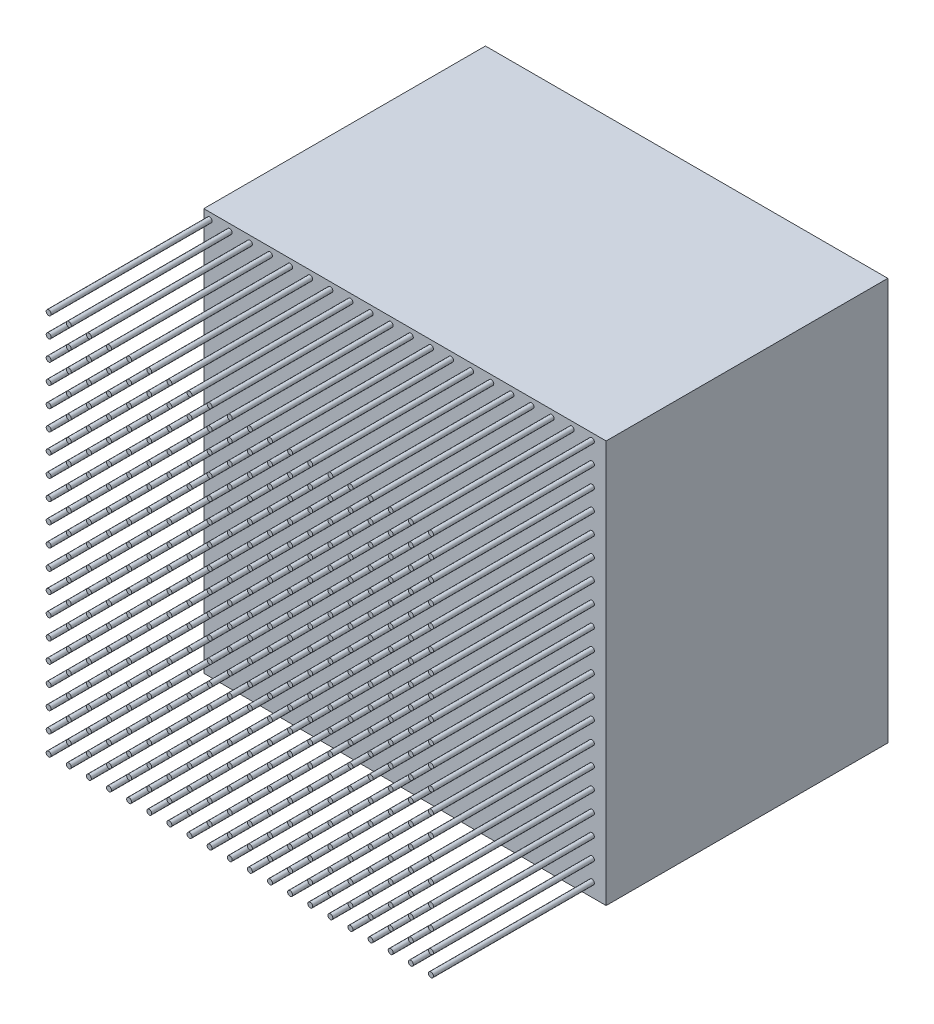
SolidWorks part; units mm, degrees
ref_plane "Front Plane" through (0, 0, 0) normal (0, 0, 1) x (1, 0, 0)
ref_plane "Top Plane" through (0, 0, 0) normal (0, 1, 0) x (1, 0, 0)
ref_plane "Right Plane" through (0, 0, 0) normal (1, 0, 0) x (0, 0, -1)
sketch "Sketch1" plane through (0, 0, 0) normal (0, 0, 1) x (1, 0, 0)
  line L1 (-50, -50) -> (50, -50)
  line L2 (-50, -50) -> (-50, 50)
  line L3 (-50, 50) -> (50, 50)
  line L4 (50, -50) -> (50, 50)
  line L5 (-50, -50) -> (50, 50) construction
  line L6 (-50, 50) -> (50, -50) construction
  point P0 (0, 0)
  dimension "D1" = 100
  dimension "D2" = 100
extrude "Boss-Extrude1" add sketch "Sketch1" along normal blind 70
sketch "Sketch2" plane through (0, 0, 70) normal (0, 0, 1) x (1, 0, 0)
  circle A0 centre (-48.544, 48.3318) radius 0.6164
  circle A1 centre (-43.544, 48.3318) radius 0.6164
  circle A2 centre (-38.544, 48.3318) radius 0.6164
  circle A3 centre (-33.544, 48.3318) radius 0.6164
  circle A4 centre (-28.544, 48.3318) radius 0.6164
  circle A5 centre (-23.544, 48.3318) radius 0.6164
  circle A6 centre (-18.544, 48.3318) radius 0.6164
  circle A7 centre (-13.544, 48.3318) radius 0.6164
  circle A8 centre (-8.544, 48.3318) radius 0.6164
  circle A9 centre (-3.544, 48.3318) radius 0.6164
  circle A10 centre (1.456, 48.3318) radius 0.6164
  circle A11 centre (6.456, 48.3318) radius 0.6164
  circle A12 centre (11.456, 48.3318) radius 0.6164
  circle A13 centre (16.456, 48.3318) radius 0.6164
  circle A14 centre (21.456, 48.3318) radius 0.6164
  circle A15 centre (26.456, 48.3318) radius 0.6164
  circle A16 centre (31.456, 48.3318) radius 0.6164
  circle A17 centre (36.456, 48.3318) radius 0.6164
  circle A18 centre (41.456, 48.3318) radius 0.6164
  circle A19 centre (46.456, 48.3318) radius 0.6164
  circle A20 centre (-43.544, 43.3318) radius 0.6164
  circle A21 centre (-38.544, 43.3318) radius 0.6164
  circle A22 centre (-33.544, 43.3318) radius 0.6164
  circle A23 centre (-28.544, 43.3318) radius 0.6164
  circle A24 centre (-23.544, 43.3318) radius 0.6164
  circle A25 centre (-18.544, 43.3318) radius 0.6164
  circle A26 centre (-13.544, 43.3318) radius 0.6164
  circle A27 centre (-8.544, 43.3318) radius 0.6164
  circle A28 centre (-3.544, 43.3318) radius 0.6164
  circle A29 centre (1.456, 43.3318) radius 0.6164
  circle A30 centre (6.456, 43.3318) radius 0.6164
  circle A31 centre (11.456, 43.3318) radius 0.6164
  circle A32 centre (16.456, 43.3318) radius 0.6164
  circle A33 centre (21.456, 43.3318) radius 0.6164
  circle A34 centre (26.456, 43.3318) radius 0.6164
  circle A35 centre (31.456, 43.3318) radius 0.6164
  circle A36 centre (36.456, 43.3318) radius 0.6164
  circle A37 centre (41.456, 43.3318) radius 0.6164
  circle A38 centre (46.456, 43.3318) radius 0.6164
  circle A39 centre (-43.544, 38.3318) radius 0.6164
  circle A40 centre (-38.544, 38.3318) radius 0.6164
  circle A41 centre (-33.544, 38.3318) radius 0.6164
  circle A42 centre (-28.544, 38.3318) radius 0.6164
  circle A43 centre (-23.544, 38.3318) radius 0.6164
  circle A44 centre (-18.544, 38.3318) radius 0.6164
  circle A45 centre (-13.544, 38.3318) radius 0.6164
  circle A46 centre (-8.544, 38.3318) radius 0.6164
  circle A47 centre (-3.544, 38.3318) radius 0.6164
  circle A48 centre (1.456, 38.3318) radius 0.6164
  circle A49 centre (6.456, 38.3318) radius 0.6164
  circle A50 centre (11.456, 38.3318) radius 0.6164
  circle A51 centre (16.456, 38.3318) radius 0.6164
  circle A52 centre (21.456, 38.3318) radius 0.6164
  circle A53 centre (26.456, 38.3318) radius 0.6164
  circle A54 centre (31.456, 38.3318) radius 0.6164
  circle A55 centre (36.456, 38.3318) radius 0.6164
  circle A56 centre (41.456, 38.3318) radius 0.6164
  circle A57 centre (46.456, 38.3318) radius 0.6164
  circle A58 centre (-43.544, 33.3318) radius 0.6164
  circle A59 centre (-38.544, 33.3318) radius 0.6164
  circle A60 centre (-33.544, 33.3318) radius 0.6164
  circle A61 centre (-28.544, 33.3318) radius 0.6164
  circle A62 centre (-23.544, 33.3318) radius 0.6164
  circle A63 centre (-18.544, 33.3318) radius 0.6164
  circle A64 centre (-13.544, 33.3318) radius 0.6164
  circle A65 centre (-8.544, 33.3318) radius 0.6164
  circle A66 centre (-3.544, 33.3318) radius 0.6164
  circle A67 centre (1.456, 33.3318) radius 0.6164
  circle A68 centre (6.456, 33.3318) radius 0.6164
  circle A69 centre (11.456, 33.3318) radius 0.6164
  circle A70 centre (16.456, 33.3318) radius 0.6164
  circle A71 centre (21.456, 33.3318) radius 0.6164
  circle A72 centre (26.456, 33.3318) radius 0.6164
  circle A73 centre (31.456, 33.3318) radius 0.6164
  circle A74 centre (36.456, 33.3318) radius 0.6164
  circle A75 centre (41.456, 33.3318) radius 0.6164
  circle A76 centre (46.456, 33.3318) radius 0.6164
  circle A77 centre (-43.544, 28.3318) radius 0.6164
  circle A78 centre (-38.544, 28.3318) radius 0.6164
  circle A79 centre (-33.544, 28.3318) radius 0.6164
  circle A80 centre (-28.544, 28.3318) radius 0.6164
  circle A81 centre (-23.544, 28.3318) radius 0.6164
  circle A82 centre (-18.544, 28.3318) radius 0.6164
  circle A83 centre (-13.544, 28.3318) radius 0.6164
  circle A84 centre (-8.544, 28.3318) radius 0.6164
  circle A85 centre (-3.544, 28.3318) radius 0.6164
  circle A86 centre (1.456, 28.3318) radius 0.6164
  circle A87 centre (6.456, 28.3318) radius 0.6164
  circle A88 centre (11.456, 28.3318) radius 0.6164
  circle A89 centre (16.456, 28.3318) radius 0.6164
  circle A90 centre (21.456, 28.3318) radius 0.6164
  circle A91 centre (26.456, 28.3318) radius 0.6164
  circle A92 centre (31.456, 28.3318) radius 0.6164
  circle A93 centre (36.456, 28.3318) radius 0.6164
  circle A94 centre (41.456, 28.3318) radius 0.6164
  circle A95 centre (46.456, 28.3318) radius 0.6164
  circle A96 centre (-43.544, 23.3318) radius 0.6164
  circle A97 centre (-38.544, 23.3318) radius 0.6164
  circle A98 centre (-33.544, 23.3318) radius 0.6164
  circle A99 centre (-28.544, 23.3318) radius 0.6164
  circle A100 centre (-23.544, 23.3318) radius 0.6164
  circle A101 centre (-18.544, 23.3318) radius 0.6164
  circle A102 centre (-13.544, 23.3318) radius 0.6164
  circle A103 centre (-8.544, 23.3318) radius 0.6164
  circle A104 centre (-3.544, 23.3318) radius 0.6164
  circle A105 centre (1.456, 23.3318) radius 0.6164
  circle A106 centre (6.456, 23.3318) radius 0.6164
  circle A107 centre (11.456, 23.3318) radius 0.6164
  circle A108 centre (16.456, 23.3318) radius 0.6164
  circle A109 centre (21.456, 23.3318) radius 0.6164
  circle A110 centre (26.456, 23.3318) radius 0.6164
  circle A111 centre (31.456, 23.3318) radius 0.6164
  circle A112 centre (36.456, 23.3318) radius 0.6164
  circle A113 centre (41.456, 23.3318) radius 0.6164
  circle A114 centre (46.456, 23.3318) radius 0.6164
  circle A115 centre (-43.544, 18.3318) radius 0.6164
  circle A116 centre (-38.544, 18.3318) radius 0.6164
  circle A117 centre (-33.544, 18.3318) radius 0.6164
  circle A118 centre (-28.544, 18.3318) radius 0.6164
  circle A119 centre (-23.544, 18.3318) radius 0.6164
  circle A120 centre (-18.544, 18.3318) radius 0.6164
  circle A121 centre (-13.544, 18.3318) radius 0.6164
  circle A122 centre (-8.544, 18.3318) radius 0.6164
  circle A123 centre (-3.544, 18.3318) radius 0.6164
  circle A124 centre (1.456, 18.3318) radius 0.6164
  circle A125 centre (6.456, 18.3318) radius 0.6164
  circle A126 centre (11.456, 18.3318) radius 0.6164
  circle A127 centre (16.456, 18.3318) radius 0.6164
  circle A128 centre (21.456, 18.3318) radius 0.6164
  circle A129 centre (26.456, 18.3318) radius 0.6164
  circle A130 centre (31.456, 18.3318) radius 0.6164
  circle A131 centre (36.456, 18.3318) radius 0.6164
  circle A132 centre (41.456, 18.3318) radius 0.6164
  circle A133 centre (46.456, 18.3318) radius 0.6164
  circle A134 centre (-43.544, 13.3318) radius 0.6164
  circle A135 centre (-38.544, 13.3318) radius 0.6164
  circle A136 centre (-33.544, 13.3318) radius 0.6164
  circle A137 centre (-28.544, 13.3318) radius 0.6164
  circle A138 centre (-23.544, 13.3318) radius 0.6164
  circle A139 centre (-18.544, 13.3318) radius 0.6164
  circle A140 centre (-13.544, 13.3318) radius 0.6164
  circle A141 centre (-8.544, 13.3318) radius 0.6164
  circle A142 centre (-3.544, 13.3318) radius 0.6164
  circle A143 centre (1.456, 13.3318) radius 0.6164
  circle A144 centre (6.456, 13.3318) radius 0.6164
  circle A145 centre (11.456, 13.3318) radius 0.6164
  circle A146 centre (16.456, 13.3318) radius 0.6164
  circle A147 centre (21.456, 13.3318) radius 0.6164
  circle A148 centre (26.456, 13.3318) radius 0.6164
  circle A149 centre (31.456, 13.3318) radius 0.6164
  circle A150 centre (36.456, 13.3318) radius 0.6164
  circle A151 centre (41.456, 13.3318) radius 0.6164
  circle A152 centre (46.456, 13.3318) radius 0.6164
  circle A153 centre (-43.544, 8.3318) radius 0.6164
  circle A154 centre (-38.544, 8.3318) radius 0.6164
  circle A155 centre (-33.544, 8.3318) radius 0.6164
  circle A156 centre (-28.544, 8.3318) radius 0.6164
  circle A157 centre (-23.544, 8.3318) radius 0.6164
  circle A158 centre (-18.544, 8.3318) radius 0.6164
  circle A159 centre (-13.544, 8.3318) radius 0.6164
  circle A160 centre (-8.544, 8.3318) radius 0.6164
  circle A161 centre (-3.544, 8.3318) radius 0.6164
  circle A162 centre (1.456, 8.3318) radius 0.6164
  circle A163 centre (6.456, 8.3318) radius 0.6164
  circle A164 centre (11.456, 8.3318) radius 0.6164
  circle A165 centre (16.456, 8.3318) radius 0.6164
  circle A166 centre (21.456, 8.3318) radius 0.6164
  circle A167 centre (26.456, 8.3318) radius 0.6164
  circle A168 centre (31.456, 8.3318) radius 0.6164
  circle A169 centre (36.456, 8.3318) radius 0.6164
  circle A170 centre (41.456, 8.3318) radius 0.6164
  circle A171 centre (46.456, 8.3318) radius 0.6164
  circle A172 centre (-43.544, 3.3318) radius 0.6164
  circle A173 centre (-38.544, 3.3318) radius 0.6164
  circle A174 centre (-33.544, 3.3318) radius 0.6164
  circle A175 centre (-28.544, 3.3318) radius 0.6164
  circle A176 centre (-23.544, 3.3318) radius 0.6164
  circle A177 centre (-18.544, 3.3318) radius 0.6164
  circle A178 centre (-13.544, 3.3318) radius 0.6164
  circle A179 centre (-8.544, 3.3318) radius 0.6164
  circle A180 centre (-3.544, 3.3318) radius 0.6164
  circle A181 centre (1.456, 3.3318) radius 0.6164
  circle A182 centre (6.456, 3.3318) radius 0.6164
  circle A183 centre (11.456, 3.3318) radius 0.6164
  circle A184 centre (16.456, 3.3318) radius 0.6164
  circle A185 centre (21.456, 3.3318) radius 0.6164
  circle A186 centre (26.456, 3.3318) radius 0.6164
  circle A187 centre (31.456, 3.3318) radius 0.6164
  circle A188 centre (36.456, 3.3318) radius 0.6164
  circle A189 centre (41.456, 3.3318) radius 0.6164
  circle A190 centre (46.456, 3.3318) radius 0.6164
  circle A191 centre (-43.544, -1.6682) radius 0.6164
  circle A192 centre (-38.544, -1.6682) radius 0.6164
  circle A193 centre (-33.544, -1.6682) radius 0.6164
  circle A194 centre (-28.544, -1.6682) radius 0.6164
  circle A195 centre (-23.544, -1.6682) radius 0.6164
  circle A196 centre (-18.544, -1.6682) radius 0.6164
  circle A197 centre (-13.544, -1.6682) radius 0.6164
  circle A198 centre (-8.544, -1.6682) radius 0.6164
  circle A199 centre (-3.544, -1.6682) radius 0.6164
  circle A200 centre (1.456, -1.6682) radius 0.6164
  circle A201 centre (6.456, -1.6682) radius 0.6164
  circle A202 centre (11.456, -1.6682) radius 0.6164
  circle A203 centre (16.456, -1.6682) radius 0.6164
  circle A204 centre (21.456, -1.6682) radius 0.6164
  circle A205 centre (26.456, -1.6682) radius 0.6164
  circle A206 centre (31.456, -1.6682) radius 0.6164
  circle A207 centre (36.456, -1.6682) radius 0.6164
  circle A208 centre (41.456, -1.6682) radius 0.6164
  circle A209 centre (46.456, -1.6682) radius 0.6164
  circle A210 centre (-43.544, -6.6682) radius 0.6164
  circle A211 centre (-38.544, -6.6682) radius 0.6164
  circle A212 centre (-33.544, -6.6682) radius 0.6164
  circle A213 centre (-28.544, -6.6682) radius 0.6164
  circle A214 centre (-23.544, -6.6682) radius 0.6164
  circle A215 centre (-18.544, -6.6682) radius 0.6164
  circle A216 centre (-13.544, -6.6682) radius 0.6164
  circle A217 centre (-8.544, -6.6682) radius 0.6164
  circle A218 centre (-3.544, -6.6682) radius 0.6164
  circle A219 centre (1.456, -6.6682) radius 0.6164
  circle A220 centre (6.456, -6.6682) radius 0.6164
  circle A221 centre (11.456, -6.6682) radius 0.6164
  circle A222 centre (16.456, -6.6682) radius 0.6164
  circle A223 centre (21.456, -6.6682) radius 0.6164
  circle A224 centre (26.456, -6.6682) radius 0.6164
  circle A225 centre (31.456, -6.6682) radius 0.6164
  circle A226 centre (36.456, -6.6682) radius 0.6164
  circle A227 centre (41.456, -6.6682) radius 0.6164
  circle A228 centre (46.456, -6.6682) radius 0.6164
  circle A229 centre (-43.544, -11.6682) radius 0.6164
  circle A230 centre (-38.544, -11.6682) radius 0.6164
  circle A231 centre (-33.544, -11.6682) radius 0.6164
  circle A232 centre (-28.544, -11.6682) radius 0.6164
  circle A233 centre (-23.544, -11.6682) radius 0.6164
  circle A234 centre (-18.544, -11.6682) radius 0.6164
  circle A235 centre (-13.544, -11.6682) radius 0.6164
  circle A236 centre (-8.544, -11.6682) radius 0.6164
  circle A237 centre (-3.544, -11.6682) radius 0.6164
  circle A238 centre (1.456, -11.6682) radius 0.6164
  circle A239 centre (6.456, -11.6682) radius 0.6164
  circle A240 centre (11.456, -11.6682) radius 0.6164
  circle A241 centre (16.456, -11.6682) radius 0.6164
  circle A242 centre (21.456, -11.6682) radius 0.6164
  circle A243 centre (26.456, -11.6682) radius 0.6164
  circle A244 centre (31.456, -11.6682) radius 0.6164
  circle A245 centre (36.456, -11.6682) radius 0.6164
  circle A246 centre (41.456, -11.6682) radius 0.6164
  circle A247 centre (46.456, -11.6682) radius 0.6164
  circle A248 centre (-43.544, -16.6682) radius 0.6164
  circle A249 centre (-38.544, -16.6682) radius 0.6164
  circle A250 centre (-33.544, -16.6682) radius 0.6164
  circle A251 centre (-28.544, -16.6682) radius 0.6164
  circle A252 centre (-23.544, -16.6682) radius 0.6164
  circle A253 centre (-18.544, -16.6682) radius 0.6164
  circle A254 centre (-13.544, -16.6682) radius 0.6164
  circle A255 centre (-8.544, -16.6682) radius 0.6164
  circle A256 centre (-3.544, -16.6682) radius 0.6164
  circle A257 centre (1.456, -16.6682) radius 0.6164
  circle A258 centre (6.456, -16.6682) radius 0.6164
  circle A259 centre (11.456, -16.6682) radius 0.6164
  circle A260 centre (16.456, -16.6682) radius 0.6164
  circle A261 centre (21.456, -16.6682) radius 0.6164
  circle A262 centre (26.456, -16.6682) radius 0.6164
  circle A263 centre (31.456, -16.6682) radius 0.6164
  circle A264 centre (36.456, -16.6682) radius 0.6164
  circle A265 centre (41.456, -16.6682) radius 0.6164
  circle A266 centre (46.456, -16.6682) radius 0.6164
  circle A267 centre (-43.544, -21.6682) radius 0.6164
  circle A268 centre (-38.544, -21.6682) radius 0.6164
  circle A269 centre (-33.544, -21.6682) radius 0.6164
  circle A270 centre (-28.544, -21.6682) radius 0.6164
  circle A271 centre (-23.544, -21.6682) radius 0.6164
  circle A272 centre (-18.544, -21.6682) radius 0.6164
  circle A273 centre (-13.544, -21.6682) radius 0.6164
  circle A274 centre (-8.544, -21.6682) radius 0.6164
  circle A275 centre (-3.544, -21.6682) radius 0.6164
  circle A276 centre (1.456, -21.6682) radius 0.6164
  circle A277 centre (6.456, -21.6682) radius 0.6164
  circle A278 centre (11.456, -21.6682) radius 0.6164
  circle A279 centre (16.456, -21.6682) radius 0.6164
  circle A280 centre (21.456, -21.6682) radius 0.6164
  circle A281 centre (26.456, -21.6682) radius 0.6164
  circle A282 centre (31.456, -21.6682) radius 0.6164
  circle A283 centre (36.456, -21.6682) radius 0.6164
  circle A284 centre (41.456, -21.6682) radius 0.6164
  circle A285 centre (46.456, -21.6682) radius 0.6164
  circle A286 centre (-43.544, -26.6682) radius 0.6164
  circle A287 centre (-38.544, -26.6682) radius 0.6164
  circle A288 centre (-33.544, -26.6682) radius 0.6164
  circle A289 centre (-28.544, -26.6682) radius 0.6164
  circle A290 centre (-23.544, -26.6682) radius 0.6164
  circle A291 centre (-18.544, -26.6682) radius 0.6164
  circle A292 centre (-13.544, -26.6682) radius 0.6164
  circle A293 centre (-8.544, -26.6682) radius 0.6164
  circle A294 centre (-3.544, -26.6682) radius 0.6164
  circle A295 centre (1.456, -26.6682) radius 0.6164
  circle A296 centre (6.456, -26.6682) radius 0.6164
  circle A297 centre (11.456, -26.6682) radius 0.6164
  circle A298 centre (16.456, -26.6682) radius 0.6164
  circle A299 centre (21.456, -26.6682) radius 0.6164
  circle A300 centre (26.456, -26.6682) radius 0.6164
  circle A301 centre (31.456, -26.6682) radius 0.6164
  circle A302 centre (36.456, -26.6682) radius 0.6164
  circle A303 centre (41.456, -26.6682) radius 0.6164
  circle A304 centre (46.456, -26.6682) radius 0.6164
  circle A305 centre (-43.544, -31.6682) radius 0.6164
  circle A306 centre (-38.544, -31.6682) radius 0.6164
  circle A307 centre (-33.544, -31.6682) radius 0.6164
  circle A308 centre (-28.544, -31.6682) radius 0.6164
  circle A309 centre (-23.544, -31.6682) radius 0.6164
  circle A310 centre (-18.544, -31.6682) radius 0.6164
  circle A311 centre (-13.544, -31.6682) radius 0.6164
  circle A312 centre (-8.544, -31.6682) radius 0.6164
  circle A313 centre (-3.544, -31.6682) radius 0.6164
  circle A314 centre (1.456, -31.6682) radius 0.6164
  circle A315 centre (6.456, -31.6682) radius 0.6164
  circle A316 centre (11.456, -31.6682) radius 0.6164
  circle A317 centre (16.456, -31.6682) radius 0.6164
  circle A318 centre (21.456, -31.6682) radius 0.6164
  circle A319 centre (26.456, -31.6682) radius 0.6164
  circle A320 centre (31.456, -31.6682) radius 0.6164
  circle A321 centre (36.456, -31.6682) radius 0.6164
  circle A322 centre (41.456, -31.6682) radius 0.6164
  circle A323 centre (46.456, -31.6682) radius 0.6164
  circle A324 centre (-43.544, -36.6682) radius 0.6164
  circle A325 centre (-38.544, -36.6682) radius 0.6164
  circle A326 centre (-33.544, -36.6682) radius 0.6164
  circle A327 centre (-28.544, -36.6682) radius 0.6164
  circle A328 centre (-23.544, -36.6682) radius 0.6164
  circle A329 centre (-18.544, -36.6682) radius 0.6164
  circle A330 centre (-13.544, -36.6682) radius 0.6164
  circle A331 centre (-8.544, -36.6682) radius 0.6164
  circle A332 centre (-3.544, -36.6682) radius 0.6164
  circle A333 centre (1.456, -36.6682) radius 0.6164
  circle A334 centre (6.456, -36.6682) radius 0.6164
  circle A335 centre (11.456, -36.6682) radius 0.6164
  circle A336 centre (16.456, -36.6682) radius 0.6164
  circle A337 centre (21.456, -36.6682) radius 0.6164
  circle A338 centre (26.456, -36.6682) radius 0.6164
  circle A339 centre (31.456, -36.6682) radius 0.6164
  circle A340 centre (36.456, -36.6682) radius 0.6164
  circle A341 centre (41.456, -36.6682) radius 0.6164
  circle A342 centre (46.456, -36.6682) radius 0.6164
  circle A343 centre (-43.544, -41.6682) radius 0.6164
  circle A344 centre (-38.544, -41.6682) radius 0.6164
  circle A345 centre (-33.544, -41.6682) radius 0.6164
  circle A346 centre (-28.544, -41.6682) radius 0.6164
  circle A347 centre (-23.544, -41.6682) radius 0.6164
  circle A348 centre (-18.544, -41.6682) radius 0.6164
  circle A349 centre (-13.544, -41.6682) radius 0.6164
  circle A350 centre (-8.544, -41.6682) radius 0.6164
  circle A351 centre (-3.544, -41.6682) radius 0.6164
  circle A352 centre (1.456, -41.6682) radius 0.6164
  circle A353 centre (6.456, -41.6682) radius 0.6164
  circle A354 centre (11.456, -41.6682) radius 0.6164
  circle A355 centre (16.456, -41.6682) radius 0.6164
  circle A356 centre (21.456, -41.6682) radius 0.6164
  circle A357 centre (26.456, -41.6682) radius 0.6164
  circle A358 centre (31.456, -41.6682) radius 0.6164
  circle A359 centre (36.456, -41.6682) radius 0.6164
  circle A360 centre (41.456, -41.6682) radius 0.6164
  circle A361 centre (46.456, -41.6682) radius 0.6164
  circle A362 centre (-43.544, -46.6682) radius 0.6164
  circle A363 centre (-38.544, -46.6682) radius 0.6164
  circle A364 centre (-33.544, -46.6682) radius 0.6164
  circle A365 centre (-28.544, -46.6682) radius 0.6164
  circle A366 centre (-23.544, -46.6682) radius 0.6164
  circle A367 centre (-18.544, -46.6682) radius 0.6164
  circle A368 centre (-13.544, -46.6682) radius 0.6164
  circle A369 centre (-8.544, -46.6682) radius 0.6164
  circle A370 centre (-3.544, -46.6682) radius 0.6164
  circle A371 centre (1.456, -46.6682) radius 0.6164
  circle A372 centre (6.456, -46.6682) radius 0.6164
  circle A373 centre (11.456, -46.6682) radius 0.6164
  circle A374 centre (16.456, -46.6682) radius 0.6164
  circle A375 centre (21.456, -46.6682) radius 0.6164
  circle A376 centre (26.456, -46.6682) radius 0.6164
  circle A377 centre (31.456, -46.6682) radius 0.6164
  circle A378 centre (36.456, -46.6682) radius 0.6164
  circle A379 centre (41.456, -46.6682) radius 0.6164
  circle A380 centre (46.456, -46.6682) radius 0.6164
  circle A381 centre (-48.544, 43.3318) radius 0.6164
  circle A382 centre (-48.544, 38.3318) radius 0.6164
  circle A383 centre (-48.544, 33.3318) radius 0.6164
  circle A384 centre (-48.544, 28.3318) radius 0.6164
  circle A385 centre (-48.544, 23.3318) radius 0.6164
  circle A386 centre (-48.544, 18.3318) radius 0.6164
  circle A387 centre (-48.544, 13.3318) radius 0.6164
  circle A388 centre (-48.544, 8.3318) radius 0.6164
  circle A389 centre (-48.544, 3.3318) radius 0.6164
  circle A390 centre (-48.544, -1.6682) radius 0.6164
  circle A391 centre (-48.544, -6.6682) radius 0.6164
  circle A392 centre (-48.544, -11.6682) radius 0.6164
  circle A393 centre (-48.544, -16.6682) radius 0.6164
  circle A394 centre (-48.544, -21.6682) radius 0.6164
  circle A395 centre (-48.544, -26.6682) radius 0.6164
  circle A396 centre (-48.544, -31.6682) radius 0.6164
  circle A397 centre (-48.544, -36.6682) radius 0.6164
  circle A398 centre (-48.544, -41.6682) radius 0.6164
  circle A399 centre (-48.544, -46.6682) radius 0.6164
  dimension "D1" = 20
  dimension "D2" = 20
extrude "Boss-Extrude2" add sketch "Sketch2" along normal blind 40
sketch "Sketch3" plane through (0, 0, 0) normal (0, 0, -1) x (-1, 0, 0)
  line L1 (-43, -43) -> (43, -43)
  line L2 (-43, -43) -> (-43, 43)
  line L3 (-43, 43) -> (43, 43)
  line L4 (43, -43) -> (43, 43)
  line L5 (-43, -43) -> (43, 43) construction
  line L6 (-43, 43) -> (43, -43) construction
  point P0 (0, 0)
  dimension "D1" = 86
  dimension "D2" = 86
extrude "Cut-Extrude1" cut sketch "Sketch3" against normal blind 27
sketch "Sketch4" plane through (0, 0, 27) normal (0, 0, -1) x (-1, 0, 0)
  line L2 (-2.767, 6.4299) -> (-2.767, 13.8964)
  line L3 (-2.767, 13.8964) -> (2.767, 13.8964)
  line L4 (2.767, 6.4299) -> (2.767, 13.8964)
  arc A0 (-2.767, 6.4299) -> (2.767, 6.4299) centre (0, 0) ccw
  point P3 (0, 7)
extrude "Cut-Extrude2" cut sketch "Sketch4" against normal blind 26
